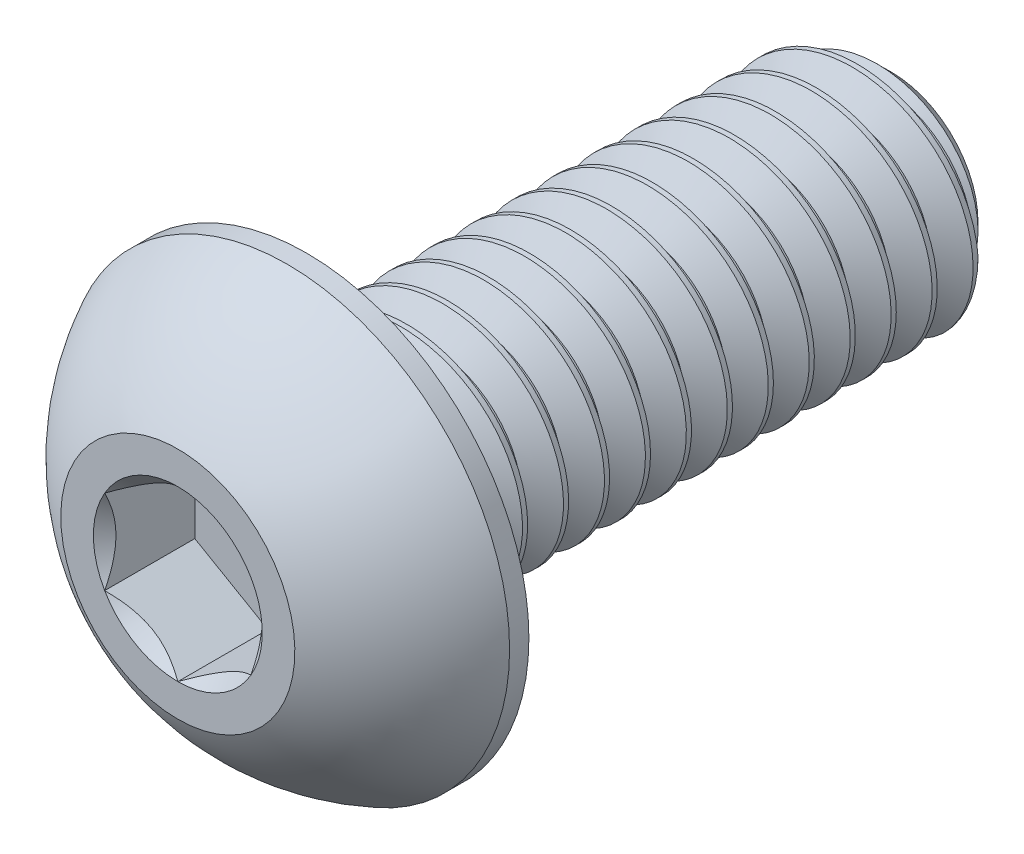
SolidWorks part; units mm, degrees
ref_plane "Front" through (0, 0, 0) normal (0, 0, 1) x (1, 0, 0)
ref_plane "Top" through (0, 0, 0) normal (0, 1, 0) x (1, 0, 0)
ref_plane "Right" through (0, 0, 0) normal (1, 0, 0) x (0, 0, -1)
sketch "Sketch1" plane through (0, 0, 0) normal (1, 0, 0) x (0, 0, -1)
  line L2 (2.2, 2) -> (12.2, 2)
  line L3 (12.2, 2) -> (12.2, 0)
  line L4 (12.2, 0) -> (2.2, 0)
  line L6 (1.87, 3.8) -> (2.2, 3.8) construction
  line L7 (12.2, 2) -> (12.2, -2) construction
  line L8 (0, 0) -> (2.2, 0) construction
  line L9 (2.2, 3.8) -> (2.2, -3.8) construction
  line L11 (2.2, 2) -> (2.2, 0)
  line L13 (0, 1.25) -> (0, -1.25) construction
  line L14 (0, 1.25) -> (0, 2) construction
  arc A3 (0, 2) -> (1.87, 3.8) centre (3.7264, 0) cw construction
  dimension "D1" = 0.33
  dimension "Head Ht" = 2.2
  dimension "Head Dia" = 7.6
  dimension "Dia" = 4
  dimension "Lg" = 10
  dimension "Hex" = 2.5
revolve "Revolve1" add sketch "Sketch1" angle 360 mid plane about L4
sketch "Sketch3" plane through (0, 0, -12.2) normal (0, 0, -1) x (-1, 0, 0)
  circle A0 centre (0, 0) radius 2
curve "Helix/Spiral1" pitch 0.7 height 10.7 radius 2 centre (0, 0, -12.2) axis (0, 0, 1) start towards (0, 1, 0)
sketch "Sketch2" plane through (0, 0, 0) normal (1, 0, 0) x (0, 0, -1)
  line L0 (12.2, 2) -> (12.8125, 2)
  line L1 (12.8125, 2) -> (12.55, 1.5453)
  line L2 (12.55, 1.5453) -> (12.4625, 1.5453)
  line L3 (12.4625, 1.5453) -> (12.2, 2)
  line L4 (12.3312, 1.7727) -> (12.6812, 1.7727) construction
  dimension "D1" = 60
  dimension "D2" = 0.0875
  dimension "D3" = 0.35
chamfer "Chamfer1" distance 0.525 angle 45 1 edges at (0, 2, -12.2)
sweep "Cut-Sweep1" cut profiles "Sketch2" path "Helix/Spiral1" align with end faces yes
sketch "Sketch7" plane through (0, 0, 0) normal (1, 0, 0) x (0, 0, -1)
  line L6 (1.87, 3.8) -> (2.2, 3.8) construction
  line L8 (0, 0) -> (2.2, 0) construction
  line L11 (2.2, 3.8) -> (2.2, -3.8) construction
  line L12 (1.87, 3.8) -> (2.2, 3.8)
  line L13 (0, 0) -> (2.2, 0)
  line L14 (0, 1.25) -> (0, -1.25) construction
  line L15 (2.2, 3.8) -> (2.2, 0)
  line L16 (0, 2) -> (0, 0)
  arc A2 (1.87, 3.8) -> (0, 2) centre (3.7264, 0) ccw construction
  arc A3 (1.87, 3.8) -> (0, 2) centre (3.7264, 0) ccw
revolve "Revolve2" add sketch "Sketch7" angle 360 mid plane about L13
sketch "Sketch5" plane through (0, 0, 0) normal (0, 0, 1) x (1, 0, 0)
  line L1 (1.25, -0.7217) -> (1.25, 0.7217)
  line L2 (1.25, 0.7217) -> (0, 1.4434)
  line L3 (0, 1.4434) -> (-1.25, 0.7217)
  line L4 (-1.25, 0.7217) -> (-1.25, -0.7217)
  line L5 (-1.25, -0.7217) -> (0, -1.4434)
  line L6 (0, -1.4434) -> (1.25, -0.7217)
  circle A0 centre (0, 0) radius 1.25 construction
extrude "Cut-Extrude2" cut sketch "Sketch5" against normal blind 1.54
sketch "Sketch6" plane through (0, 0, 0) normal (0, 0, 1) x (1, 0, 0)
  circle A0 centre (0, 0) radius 1.4434
extrude "Cut-Extrude3" cut sketch "Sketch6" against normal blind 1.54 draft 45
sketch "Sketch9" [suppressed] plane through (0, 0, -2.2) normal (0, 0, 1) x (1, 0, 0)
  circle A2 centre (0, 0) radius 2
extrude "Boss-Extrude2" [suppressed] add sketch "Sketch9" against normal offset from surface (5 mm away) 28.575 up to face at (0, 1.475, -12.2)
sketch "Sketch10" plane through (0, 0, 0) normal (1, 0, 0) x (0, 0, -1)
  line L0 (12.2, 2) -> (12.2, -2) construction
  point P0 (11.15, -2)
  dimension "D1" = 1.05
equation "\"D3@Helix/Spiral1\" = \"Lg@Sketch1\" + \"D4@Helix/Spiral1\""
equation "\"D2@Sketch2\" = \"D4@Helix/Spiral1\" * .125"
equation "\"D3@Sketch2\" = \"D4@Helix/Spiral1\" * .5"
equation "\"D1@Chamfer1\" = \"D4@Helix/Spiral1\" * .75"
equation "\"D1@Cut-Extrude2\" = \"Head Ht@Sketch1\" * .7"
equation "\"D1@Sketch1\" = \"Head Ht@Sketch1\" * .15"
equation "\"D1@Sketch10\" = \"D4@Helix/Spiral1\" * 1.5"
equation "\"D1@Cut-Extrude3\" = \"D1@Cut-Extrude2\""
